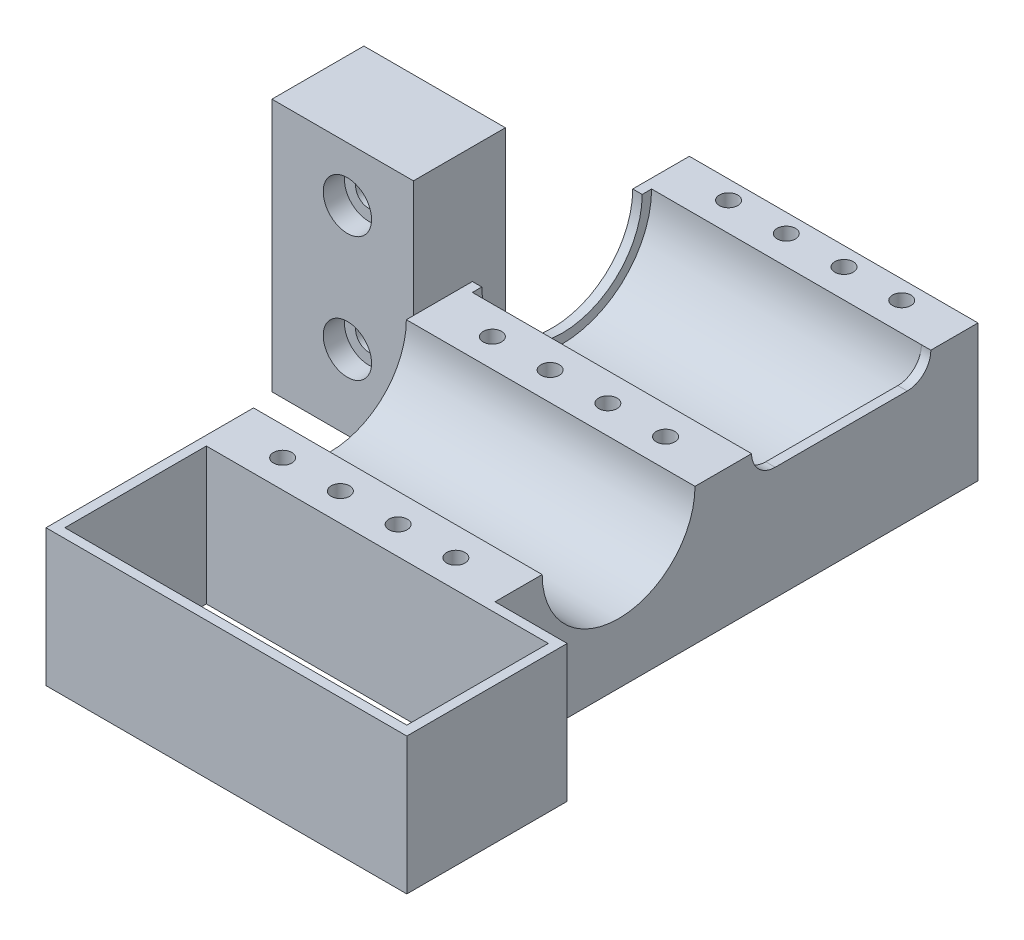
SolidWorks part; units mm, degrees
ref_plane "Front Plane" through (0, 0, 0) normal (0, 0, 1) x (1, 0, 0)
ref_plane "Top Plane" through (0, 0, 0) normal (0, 1, 0) x (1, 0, 0)
ref_plane "Right Plane" through (0, 0, 0) normal (1, 0, 0) x (0, 0, -1)
sketch "Sketch1" plane through (0, 0, 0) normal (1, 0, 0) x (0, 0, -1)
  line L0 (51.2, 42.0261) -> (51.2, 0) construction
  line L1 (0, 0) -> (102.4, 0)
  line L2 (0, 0) -> (0, 29)
  line L3 (102.4, 0) -> (102.4, 29)
  line L4 (0, 29) -> (10, 29) construction
  line L6 (42.4, 29) -> (54.4, 29) construction
  line L7 (42.4, 29) -> (54.4, 29)
  line L8 (0, 29) -> (10, 29)
  line L10 (42.4, 29) -> (54.4, 29)
  line L11 (92.4, 29) -> (102.4, 29)
  arc A0 (10, 29) -> (42.4, 29) centre (26.2, 29) ccw
  arc A1 (54.4, 29) -> (92.4, 29) centre (73.4, 29) ccw
  point P15 (73.4, 10)
  dimension "D3" = 19
  dimension "D4" = 16.2
  dimension "D1" = 10
  dimension "D2" = 12
  dimension "D5" = 10
extrude "Boss-Extrude1" add sketch "Sketch1" along normal blind 61.2 contours L8 L2 L1 L3 L7 region at (0, 11.0871, -50.0531)
sketch "Sketch7" plane through (0, 0, 0) normal (-1, 0, 0) x (0, 0, 1)
  line L0 (0, 0) -> (-102.4, 0) construction
  line L1 (-63.4, 0) -> (-43.8992, 0)
  line L2 (-63.4, 0) -> (-63.4, 53.7409)
  line L3 (-63.4, 53.7409) -> (-43.8992, 53.7409)
  line L4 (-43.8992, 0) -> (-43.8992, 53.7409)
  line L5 (-42.4, 29) -> (-54.4, 29) construction
  line L6 (-42.4, 29) -> (-54.4, 29) construction
  arc A0 (-92.4, 29) -> (-54.4, 29) centre (-73.4, 29) ccw construction
  arc A1 (-92.4, 29) -> (-54.4, 29) centre (-73.4, 29) ccw construction
  circle A2 centre (-73.4, 29) radius 6 construction
  dimension "D1" = 12
  dimension "D2" = 10
  dimension "D3" = 1.4992
extrude "Boss-Extrude2" add sketch "Sketch7" along normal blind 30
sketch "Sketch14" plane through (61.2, 0, 0) normal (1, 0, 0) x (0, 0, -1)
  line L0 (54.4, 29) -> (92.4, 29)
  arc A0 (54.4, 29) -> (92.4, 29) centre (73.4, 29) ccw construction
  arc A1 (54.4, 29) -> (92.4, 29) centre (73.4, 29) ccw
extrude "Boss-Extrude3" add sketch "Sketch14" against normal blind 2
sketch "Sketch19" plane through (0, 0, 0) normal (-1, 0, 0) x (0, 0, 1)
  line L1 (-90.4, 29) -> (-92.4, 29)
  line L2 (-56.4, 29) -> (-54.4, 29)
  arc A5 (-63.4, 12.8445) -> (-54.4, 29) centre (-73.4, 29) ccw construction
  arc A7 (-92.4, 29) -> (-63.4, 12.8445) centre (-73.4, 29) ccw construction
  arc A8 (-63.4, 12.8445) -> (-54.4, 29) centre (-73.4, 29) ccw
  arc A9 (-92.4, 29) -> (-63.4, 12.8445) centre (-73.4, 29) ccw
  arc A10 (-90.4, 29) -> (-64.4526, 14.5451) centre (-73.4, 29) ccw
  arc A11 (-64.4526, 14.5451) -> (-56.4, 29) centre (-73.4, 29) ccw
  dimension "D1" = 2
extrude "Boss-Extrude4" add sketch "Sketch19" against normal blind 2
sketch "Sketch26" plane through (0, 0, 0) normal (0, 1, 0) x (1, 0, 0)
  line L0 (2, -2) -> (74.5, -2)
  line L1 (0, 0) -> (76.5, 0)
  line L2 (0, 0) -> (0, -34)
  line L3 (0, -34) -> (76.5, -34)
  line L4 (76.5, 0) -> (76.5, -34)
  line L5 (74.5, -2) -> (74.5, -32)
  line L6 (2, -32) -> (74.5, -32)
  line L7 (2, -2) -> (2, -32)
  dimension "D1" = 34
  dimension "D2" = 76.5
  dimension "D3" = 2
extrude "Boss-Extrude5" add sketch "Sketch26" along normal blind 29
sketch "Sketch8" plane through (0, 0, -63.4) normal (0, 0, -1) x (-1, 0, 0)
  line L0 (30, 53.7409) -> (0, 53.7409) construction
  line L1 (0, 53.7409) -> (0, 15.2523) construction
  line L2 (30, 53.7409) -> (0, 53.7409) construction
  line L3 (0, 53.7409) -> (0, 15.2523) construction
  line L5 (-2, 29) -> (0, 29) construction
  line L12 (3.5, 29) -> (45.8321, 29) construction
  line L14 (-2, 29) -> (-2, 10) construction
  line L15 (-2, 29) -> (-2, 10) construction
  line L16 (-2, 29) -> (0, 29) construction
  circle A0 centre (14, 42.2) radius 2.75
  circle A1 centre (14, 15.8) radius 2.75
  point P2 (12.9314, 18.0951)
  point P5 (0, 0)
  dimension "D3" = 5.5
  dimension "D2" = 14
  dimension "D1" = 13.2
  dimension "D4" = 13.2
extrude "Cut-Extrude1" cut sketch "Sketch8" against normal up to surface (19.5008 mm away) up to face at (-12, 27.2964, -43.8992)
sketch "Sketch9" plane through (0, 0, -63.4) normal (0, 0, -1) x (-1, 0, 0)
  circle A0 centre (14, 42.2) radius 5.125
  circle A1 centre (14, 15.8) radius 5.125
  point P4 (11.6902, 46.8493)
  point P6 (11.9613, 20.4493)
  dimension "D1" = 10.25
extrude "Cut-Extrude2" cut sketch "Sketch9" against normal blind 4.5
sketch "Sketch10" plane through (0, 0, -43.8992) normal (0, 0, 1) x (1, 0, 0)
  circle A0 centre (-14, 42.2) radius 5.125
  circle A1 centre (-14, 15.8) radius 5.125
  point P1 (-15.8906, 46.8493)
  point P6 (-15.8799, 20.4493)
  dimension "D1" = 10.25
extrude "Cut-Extrude8" cut sketch "Sketch10" against normal blind 4.5
sketch "Sketch22" plane through (0, 29, 0) normal (0, 1, 0) x (1, 0, 0)
  line L0 (61.2, 42.4) -> (0, 42.4) construction
  line L1 (59.2, 54.4) -> (2, 54.4) construction
  line L2 (61.2, 42.4) -> (0, 42.4) construction
  line L3 (59.2, 54.4) -> (2, 54.4) construction
  line L4 (30.6, 54.4) -> (30.6, 42.4) construction
  line L5 (30.6, 48.4) -> (0, 48.4) construction
  line L6 (30.6, 48.4) -> (61.2, 48.4) construction
  line L7 (61.2, 42.4) -> (61.2, 102.4) construction
  line L8 (61.2, 10) -> (61.2, 42.4) construction
  line L9 (59.2, 92.4) -> (59.2, 54.4) construction
  line L10 (61.2, 10) -> (61.2, 42.4) construction
  line L11 (59.2, 92.4) -> (59.2, 54.4) construction
  line L12 (59.2, 73.4) -> (-4.6102, 73.4) construction
  line L13 (61.2, 26.2) -> (-9.4707, 26.2) construction
  line L14 (-21.9217, 98.47) -> (51.6485, 98.47) construction
  line L15 (76.5, 0) -> (61.2, 0) construction
  line L16 (10.6744, 3.93) -> (59.5979, 3.93) construction
  line L17 (0, 43.8992) -> (0, 63.4) construction
  line L18 (61.2, 102.4) -> (0, 102.4) construction
  line L19 (0, 43.8992) -> (0, 63.4) construction
  circle A0 centre (12.24, 48.4) radius 1.95
  circle A1 centre (24.48, 48.4) radius 1.95
  circle A2 centre (36.72, 48.4) radius 1.95
  circle A3 centre (48.96, 48.4) radius 1.95
  circle A5 centre (48.96, 98.47) radius 1.95
  circle A8 centre (24.48, 98.47) radius 1.95
  circle A9 centre (12.24, 98.47) radius 1.95
  circle A10 centre (36.72, 3.93) radius 1.95
  circle A11 centre (48.96, 3.93) radius 1.95
  circle A14 centre (12.24, 3.93) radius 1.95
  circle A15 centre (36.72, 98.47) radius 1.95
  circle A16 centre (24.48, 3.93) radius 1.95
  dimension "D1" = 3.9
  dimension "D7" = 3.93
  dimension "D8" = 3.93
  dimension "D2" = 12.24
  dimension "D3" = 61.2
  dimension "D4" = 12.24
  dimension "D5" = 12.24
  dimension "D6" = 12.24
extrude "Cut-Extrude9" cut sketch "Sketch22" against normal up to surface (29 mm away) up to face at (21.54, 0, -35.1398)
sketch "Sketch24" plane through (0, 0, 0) normal (0, -1, 0) x (1, 0, 0)
  line L0 (74.5, 2) -> (2, 2) construction
  line L1 (15.7041, -3.93) -> (13.9721, -0.93)
  line L2 (13.9721, -0.93) -> (10.5079, -0.93)
  line L3 (10.5079, -0.93) -> (8.7759, -3.93)
  line L4 (8.7759, -3.93) -> (10.5079, -6.93)
  line L5 (10.5079, -6.93) -> (13.9721, -6.93)
  line L6 (13.9721, -6.93) -> (15.7041, -3.93)
  line L7 (27.9441, -3.93) -> (26.2121, -0.93)
  line L8 (26.2121, -0.93) -> (22.7479, -0.93)
  line L9 (22.7479, -0.93) -> (21.0159, -3.93)
  line L10 (21.0159, -3.93) -> (22.7479, -6.93)
  line L11 (22.7479, -6.93) -> (26.2121, -6.93)
  line L12 (26.2121, -6.93) -> (27.9441, -3.93)
  line L13 (40.1841, -3.93) -> (38.4521, -0.93)
  line L14 (38.4521, -0.93) -> (34.9879, -0.93)
  line L15 (34.9879, -0.93) -> (33.2559, -3.93)
  line L16 (33.2559, -3.93) -> (34.9879, -6.93)
  line L17 (34.9879, -6.93) -> (38.4521, -6.93)
  line L18 (38.4521, -6.93) -> (40.1841, -3.93)
  line L19 (52.4241, -3.93) -> (50.6921, -0.93)
  line L20 (50.6921, -0.93) -> (47.2279, -0.93)
  line L21 (47.2279, -0.93) -> (45.4959, -3.93)
  line L22 (45.4959, -3.93) -> (47.2279, -6.93)
  line L23 (47.2279, -6.93) -> (50.6921, -6.93)
  line L24 (50.6921, -6.93) -> (52.4241, -3.93)
  line L25 (45.4959, -48.4009) -> (47.2287, -51.4005)
  line L26 (47.2287, -51.4005) -> (50.6928, -51.3995)
  line L27 (50.6928, -51.3995) -> (52.4241, -48.3991)
  line L28 (52.4241, -48.3991) -> (50.6913, -45.3995)
  line L29 (50.6913, -45.3995) -> (47.2272, -45.4005)
  line L30 (47.2272, -45.4005) -> (45.4959, -48.4009)
  line L31 (33.2559, -48.4007) -> (34.9885, -51.4003)
  line L32 (34.9885, -51.4003) -> (38.4526, -51.3997)
  line L33 (38.4526, -51.3997) -> (40.1841, -48.3993)
  line L34 (40.1841, -48.3993) -> (38.4515, -45.3997)
  line L35 (38.4515, -45.3997) -> (34.9874, -45.4003)
  line L36 (34.9874, -45.4003) -> (33.2559, -48.4007)
  line L37 (21.0159, -48.4005) -> (22.7484, -51.4003)
  line L38 (22.7484, -51.4003) -> (26.2125, -51.3997)
  line L39 (26.2125, -51.3997) -> (27.9441, -48.3995)
  line L40 (27.9441, -48.3995) -> (26.2116, -45.3997)
  line L41 (26.2116, -45.3997) -> (22.7475, -45.4003)
  line L42 (22.7475, -45.4003) -> (21.0159, -48.4005)
  line L43 (8.7759, -48.4005) -> (10.5083, -51.4002)
  line L44 (10.5083, -51.4002) -> (13.9724, -51.3998)
  line L45 (13.9724, -51.3998) -> (15.7041, -48.3995)
  line L46 (15.7041, -48.3995) -> (13.9717, -45.3998)
  line L47 (13.9717, -45.3998) -> (10.5076, -45.4002)
  line L48 (10.5076, -45.4002) -> (8.7759, -48.4005)
  line L49 (10.5079, -95.47) -> (8.7759, -98.47)
  line L50 (8.7759, -98.47) -> (10.5079, -101.47)
  line L51 (10.5079, -101.47) -> (13.9721, -101.47)
  line L52 (13.9721, -101.47) -> (15.7041, -98.47)
  line L53 (15.7041, -98.47) -> (13.9721, -95.47)
  line L54 (13.9721, -95.47) -> (10.5079, -95.47)
  line L55 (22.7479, -95.47) -> (21.0159, -98.47)
  line L56 (21.0159, -98.47) -> (22.7479, -101.47)
  line L57 (22.7479, -101.47) -> (26.2121, -101.47)
  line L58 (26.2121, -101.47) -> (27.9441, -98.47)
  line L59 (27.9441, -98.47) -> (26.2121, -95.47)
  line L60 (26.2121, -95.47) -> (22.7479, -95.47)
  line L61 (34.9879, -95.47) -> (33.2559, -98.47)
  line L62 (33.2559, -98.47) -> (34.9879, -101.47)
  line L63 (34.9879, -101.47) -> (38.4521, -101.47)
  line L64 (38.4521, -101.47) -> (40.1841, -98.47)
  line L65 (40.1841, -98.47) -> (38.4521, -95.47)
  line L66 (38.4521, -95.47) -> (34.9879, -95.47)
  line L67 (47.2279, -95.47) -> (45.4959, -98.47)
  line L68 (45.4959, -98.47) -> (47.2279, -101.47)
  line L69 (47.2279, -101.47) -> (50.6921, -101.47)
  line L70 (50.6921, -101.47) -> (52.4241, -98.47)
  line L71 (52.4241, -98.47) -> (50.6921, -95.47)
  line L72 (50.6921, -95.47) -> (47.2279, -95.47)
  line L73 (61.2, -102.4) -> (0, -102.4) construction
  circle A0 centre (12.24, -3.93) radius 3 construction
  circle A1 centre (24.48, -3.93) radius 3 construction
  circle A2 centre (36.72, -3.93) radius 3 construction
  circle A3 centre (48.96, -3.93) radius 3 construction
  circle A4 centre (48.96, -48.4) radius 3 construction
  circle A5 centre (36.72, -48.4) radius 3 construction
  circle A6 centre (24.48, -48.4) radius 3 construction
  circle A7 centre (12.24, -48.4) radius 3 construction
  circle A8 centre (12.24, -98.47) radius 3 construction
  circle A9 centre (24.48, -98.47) radius 3 construction
  circle A10 centre (36.72, -98.47) radius 3 construction
  circle A11 centre (48.96, -98.47) radius 3 construction
  dimension "D1" = 6
extrude "Cut-Extrude10" cut sketch "Sketch24" against normal blind 4.5
sketch "Sketch25" plane through (61.2, 0, 0) normal (1, 0, 0) x (0, 0, -1)
  line L0 (59.4, 29) -> (87.4, 29) construction
  line L1 (42.4, 29) -> (102.4, 29) construction
  line L2 (59.4, 34) -> (87.4, 34)
  line L3 (59.4, 24) -> (87.4, 24)
  line L6 (92.4, 29) -> (54.4, 29) construction
  line L7 (92.4, 29) -> (54.4, 29) construction
  arc A0 (59.4, 34) -> (59.4, 24) centre (59.4, 29) ccw
  arc A1 (87.4, 24) -> (87.4, 34) centre (87.4, 29) ccw
  point P5 (73.4, 29)
  point P12 (92.4, 29)
  dimension "D1" = 10
extrude "Cut-Extrue11" cut sketch "Sketch25" against normal blind 2
chamfer "Chamfer1" [suppressed] distance 1 angle 45
split "Split1" bodies to split 126 resulting bodies 128 129 split by face at (0, 35.9789, -53.8698)
equation "\"MotorDIA\"= 37' Motor Diameter"
equation "\"SyringeDIA\"= 31.4'60ml Syringe Diameter"
equation "\"MotorShaftDIA\"= 6'Motor Shaft Dia"
equation "\"MotorKeyway\"= 1'Motor Shaft Keyway Depth"
equation "\"MotorLength\"= 56.7'Motor Length Excluding Shaft"
equation "\"SyringeLength\"= 117.3'60ml Syringe Length Excluding Nozzle"
equation "\"3Dtol\"= .5'Sizing Tolerance for 3D printed parts"
equation "\"ChamberDIA\"= 100 - 4'Buoyancy Chamber inner Diameter"
equation "\"ChamberThk\"= 2mm'Buoyancy Chamber Wall Thickness"
equation "\"D4@Sketch1\"=\"SyringeDIA\"/2+\"3Dtol\""
equation "\"D3@Sketch1\"=\"MotorDIA\"/2+\"3Dtol\""
equation "\"D1@Boss-Extrude1\"=\"MotorLength\"+\"3Dtol\"+4"
equation "\"D4@Sketch8\"=\"D1@Sketch8\""
equation "\"BearingOD\"= 10"
equation "\"BearingID\"= 4"
equation "\"Bearingwidth\"= 4"
equation "\"ShaftDIA\"= 4"
equation "\"D2@Sketch22\"=\"D3@Sketch22\"/5"
equation "\"D4@Sketch22\"=\"D2@Sketch22\""
equation "\"D5@Sketch22\"=\"D4@Sketch22\""
equation "\"D6@Sketch22\"=\"D5@Sketch22\""
